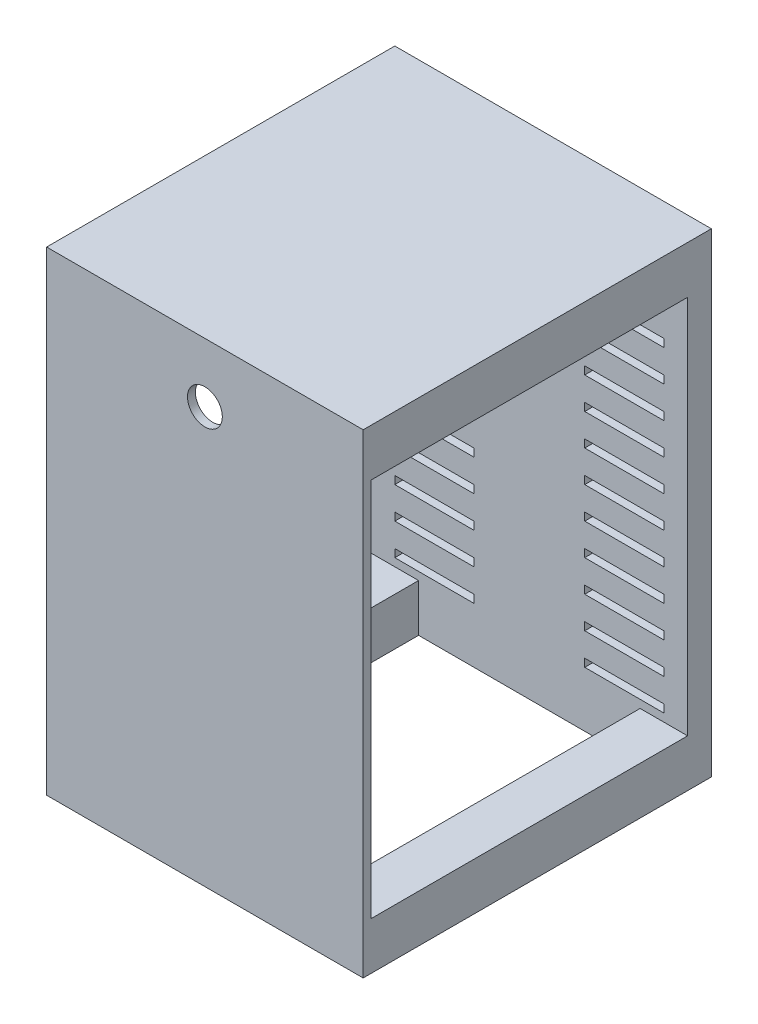
SolidWorks part; units mm, degrees
ref_plane "Alzado" through (0, 0, 0) normal (0, 0, 1) x (1, 0, 0)
ref_plane "Planta" through (0, 0, 0) normal (0, 1, 0) x (1, 0, 0)
ref_plane "Vista lateral" through (0, 0, 0) normal (1, 0, 0) x (0, 0, -1)
sketch "Croquis1" plane through (0, 0, 0) normal (0, 0, 1) x (1, 0, 0)
  line L1 (-100, -150) -> (100, -150)
  line L2 (-100, -150) -> (-100, 150)
  line L3 (-100, 150) -> (100, 150)
  line L4 (100, -150) -> (100, 150)
  line L5 (-100, -150) -> (100, 150) construction
  line L6 (-100, 150) -> (100, -150) construction
  point P0 (0, 0)
  dimension "D1" = 200
  dimension "D2" = 300
extrude "Saliente-Extruir2" add sketch "Croquis1" along normal blind 15 contours L3 L4 L1 L2
sketch "Croquis2" plane through (0, 0, 15) normal (0, 0, 1) x (1, 0, 0)
  line L1 (-100, 150) -> (-70, 150)
  line L2 (-100, 150) -> (-100, 120)
  line L3 (-100, 120) -> (-70, 120)
  line L4 (-70, 150) -> (-70, 120)
  line L5 (100, 150) -> (70, 150)
  line L6 (100, 150) -> (100, 120)
  line L7 (100, 120) -> (70, 120)
  line L8 (70, 150) -> (70, 120)
  line L9 (-100, -150) -> (-70, -150)
  line L10 (-100, -150) -> (-100, -120)
  line L11 (-100, -120) -> (-70, -120)
  line L12 (-70, -150) -> (-70, -120)
  line L13 (100, -150) -> (70, -150)
  line L14 (100, -150) -> (100, -120)
  line L15 (100, -120) -> (70, -120)
  line L16 (70, -150) -> (70, -120)
  dimension "D1" = 30
  dimension "D2" = 30
extrude "Saliente-Extruir3" add sketch "Croquis2" along normal blind 200
sketch "Croquis3" plane through (0, 0, 215) normal (0, 0, 1) x (1, 0, 0)
  line L1 (-100, 150) -> (100, 150)
  line L2 (-100, 150) -> (-100, -150)
  line L3 (-100, -150) -> (100, -150)
  line L4 (100, 150) -> (100, -150)
extrude "Saliente-Extruir4" add sketch "Croquis3" along normal blind 5
sketch "Croquis7" plane through (0, 0, 0) normal (0, 0, -1) x (-1, 0, 0)
  line L0 (35, 110) -> (85, 110)
  line L1 (-85, 110) -> (-35, 110)
  line L2 (-85, 110) -> (-85, 105)
  line L3 (-85, 105) -> (-35, 105)
  line L4 (-35, 110) -> (-35, 105)
  line L5 (85, 110) -> (85, 105)
  line L6 (35, 105) -> (85, 105)
  line L7 (35, 110) -> (35, 105)
  line L8 (35, 90) -> (85, 90)
  line L9 (85, 90) -> (85, 85)
  line L10 (35, 85) -> (85, 85)
  line L11 (35, 90) -> (35, 85)
  line L12 (35, 70) -> (85, 70)
  line L13 (85, 70) -> (85, 65)
  line L14 (35, 65) -> (85, 65)
  line L15 (35, 70) -> (35, 65)
  line L16 (35, 50) -> (85, 50)
  line L17 (85, 50) -> (85, 45)
  line L18 (35, 45) -> (85, 45)
  line L19 (35, 50) -> (35, 45)
  line L20 (35, 30) -> (85, 30)
  line L21 (85, 30) -> (85, 25)
  line L22 (35, 25) -> (85, 25)
  line L23 (35, 30) -> (35, 25)
  line L24 (35, 10) -> (85, 10)
  line L25 (85, 10) -> (85, 5)
  line L26 (35, 5) -> (85, 5)
  line L27 (35, 10) -> (35, 5)
  line L28 (35, -10) -> (85, -10)
  line L29 (85, -10) -> (85, -15)
  line L30 (35, -15) -> (85, -15)
  line L31 (35, -10) -> (35, -15)
  line L32 (35, -30) -> (85, -30)
  line L33 (85, -30) -> (85, -35)
  line L34 (35, -35) -> (85, -35)
  line L35 (35, -30) -> (35, -35)
  line L36 (35, -50) -> (85, -50)
  line L37 (85, -50) -> (85, -55)
  line L38 (35, -55) -> (85, -55)
  line L39 (35, -50) -> (35, -55)
  line L40 (35, -70) -> (85, -70)
  line L41 (85, -70) -> (85, -75)
  line L42 (35, -75) -> (85, -75)
  line L43 (35, -70) -> (35, -75)
  line L64 (-85, 90) -> (-35, 90)
  line L65 (-35, 90) -> (-35, 85)
  line L66 (-85, 85) -> (-35, 85)
  line L67 (-85, 90) -> (-85, 85)
  line L68 (-85, 70) -> (-35, 70)
  line L69 (-35, 70) -> (-35, 65)
  line L70 (-85, 65) -> (-35, 65)
  line L71 (-85, 70) -> (-85, 65)
  line L72 (-85, 50) -> (-35, 50)
  line L73 (-35, 50) -> (-35, 45)
  line L74 (-85, 45) -> (-35, 45)
  line L75 (-85, 50) -> (-85, 45)
  line L76 (-85, 30) -> (-35, 30)
  line L77 (-35, 30) -> (-35, 25)
  line L78 (-85, 25) -> (-35, 25)
  line L79 (-85, 30) -> (-85, 25)
  line L80 (-85, 10) -> (-35, 10)
  line L81 (-35, 10) -> (-35, 5)
  line L82 (-85, 5) -> (-35, 5)
  line L83 (-85, 10) -> (-85, 5)
  line L84 (-85, -10) -> (-35, -10)
  line L85 (-35, -10) -> (-35, -15)
  line L86 (-85, -15) -> (-35, -15)
  line L87 (-85, -10) -> (-85, -15)
  line L88 (-85, -30) -> (-35, -30)
  line L89 (-35, -30) -> (-35, -35)
  line L90 (-85, -35) -> (-35, -35)
  line L91 (-85, -30) -> (-85, -35)
  line L92 (-85, -50) -> (-35, -50)
  line L93 (-35, -50) -> (-35, -55)
  line L94 (-85, -55) -> (-35, -55)
  line L95 (-85, -50) -> (-85, -55)
  line L96 (-85, -70) -> (-35, -70)
  line L97 (-35, -70) -> (-35, -75)
  line L98 (-85, -75) -> (-35, -75)
  line L99 (-85, -70) -> (-85, -75)
  line L120 (-85, -90) -> (-35, -90)
  line L121 (-35, -90) -> (-35, -95)
  line L122 (-85, -95) -> (-35, -95)
  line L123 (-85, -90) -> (-85, -95)
  line L124 (35, -90) -> (85, -90)
  line L125 (85, -90) -> (85, -95)
  line L126 (35, -95) -> (85, -95)
  line L127 (35, -90) -> (35, -95)
  line L128 (-85, -110) -> (-35, -110)
  line L129 (-35, -110) -> (-35, -115)
  line L130 (-85, -115) -> (-35, -115)
  line L131 (-85, -110) -> (-85, -115)
  line L132 (35, -110) -> (85, -110)
  line L133 (85, -110) -> (85, -115)
  line L134 (35, -115) -> (85, -115)
  line L135 (35, -110) -> (35, -115)
  line L152 (-85, 110) -> (-85, 150) construction
  line L153 (100, 150) -> (-100, 150) construction
  line L154 (-85, 110) -> (-100, 110) construction
  line L155 (-100, -150) -> (-100, 150) construction
  line L156 (-85, 105) -> (-100, 105) construction
  line L157 (85, 110) -> (100, 110) construction
  line L158 (100, -150) -> (100, 150) construction
  line L159 (-85, -130) -> (-35, -130) [skipped]
  line L160 (-35, -130) -> (-35, -135) [skipped]
  line L161 (-85, -135) -> (-35, -135) [skipped]
  line L162 (-85, -130) -> (-85, -135) [skipped]
  line L219 (-85, -150) -> (-35, -150) [skipped]
  line L220 (-35, -150) -> (-35, -155) [skipped]
  line L221 (-85, -155) -> (-35, -155) [skipped]
  line L222 (-85, -150) -> (-85, -155) [skipped]
  line L223 (35, -150) -> (85, -150) [skipped]
  line L224 (85, -150) -> (85, -155) [skipped]
  line L225 (35, -155) -> (85, -155) [skipped]
  line L226 (35, -150) -> (35, -155) [skipped]
  line L227 (35, -130) -> (85, -130) [skipped]
  line L228 (85, -130) -> (85, -135) [skipped]
  line L229 (35, -135) -> (85, -135) [skipped]
  line L230 (35, -130) -> (35, -135) [skipped]
  dimension "D1" = 5
  dimension "D2" = 50
  dimension "D5" = 40
  dimension "D3" = 2
  dimension "D4" = 14
extrude "Cortar-Extruir1" cut sketch "Croquis7" against normal blind 20
sketch "Croquis9" plane through (0, 150, 0) normal (0, 1, 0) x (1, 0, 0)
  line L1 (100, -220) -> (-100, -220)
  line L2 (100, -220) -> (100, 0)
  line L3 (100, 0) -> (-100, 0)
  line L4 (-100, -220) -> (-100, 0)
extrude "Saliente-Extruir6" add sketch "Croquis9" against normal blind 5
sketch "Croquis11" plane through (0, 0, 220) normal (0, 0, 1) x (1, 0, 0)
  circle A0 centre (0, 112.5528) radius 11
  dimension "D1" = 22
extrude "Cortar-Extruir3" cut sketch "Croquis11" against normal blind 10
